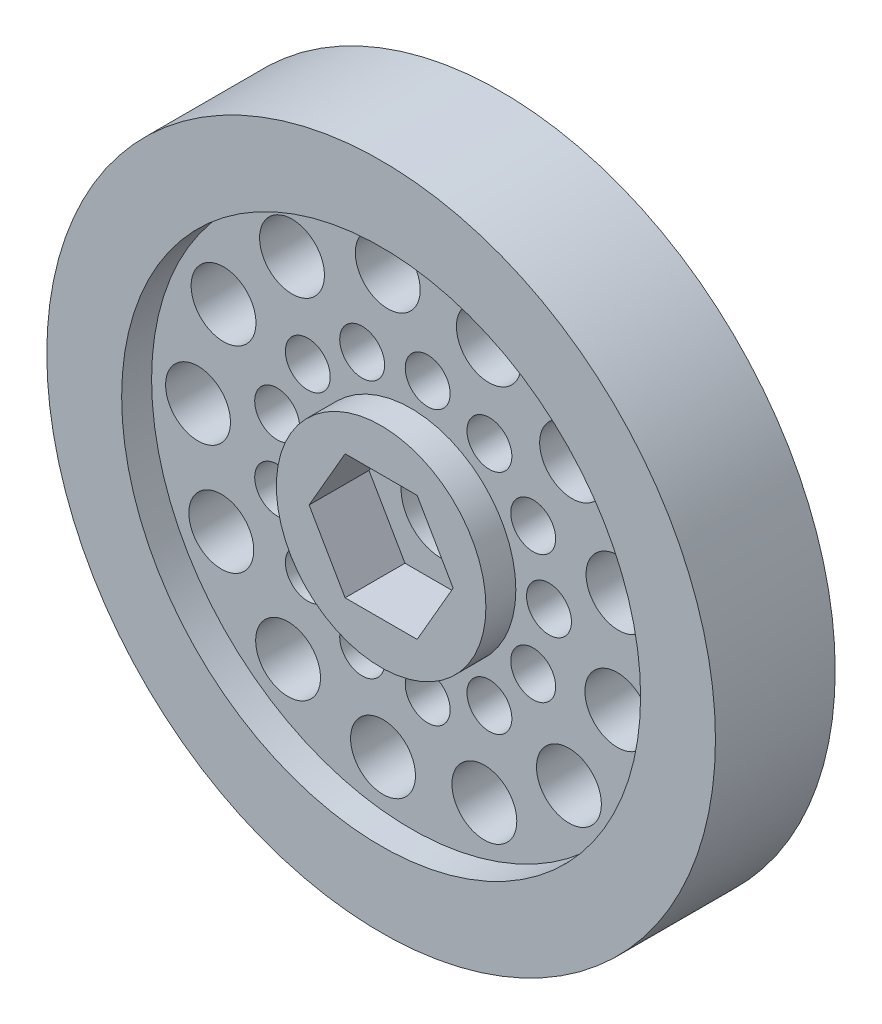
SolidWorks part; units mm, degrees
ref_plane "Front Plane" through (0, 0, 0) normal (0, 0, 1) x (1, 0, 0)
ref_plane "Top Plane" through (0, 0, 0) normal (0, 1, 0) x (1, 0, 0)
ref_plane "Right Plane" through (0, 0, 0) normal (1, 0, 0) x (0, 0, -1)
sketch "Sketch1" plane through (0, 0, 0) normal (0, 0, 1) x (1, 0, 0)
  circle A0 centre (0, 0) radius 4
  circle A1 centre (0, 0) radius 33.5
  dimension "D1" = 67
  dimension "D2" = 8
extrude "Boss-Extrude1" add sketch "Sketch1" along normal blind 12
sketch "Sketch2" plane through (0, 0, 12) normal (0, 0, 1) x (1, 0, 0)
  line L1 (7.2169, 0) -> (3.6084, 6.25)
  line L2 (3.6084, 6.25) -> (-3.6084, 6.25)
  line L3 (-3.6084, 6.25) -> (-7.2169, 0)
  line L4 (-7.2169, 0) -> (-3.6084, -6.25)
  line L5 (-3.6084, -6.25) -> (3.6084, -6.25)
  line L6 (3.6084, -6.25) -> (7.2169, 0)
  circle A0 centre (0, 0) radius 6.25 construction
  dimension "D1" = 12.5
extrude "Cut-Extrude1" cut sketch "Sketch2" against normal blind 6
sketch "Sketch3" plane through (0, 0, 12) normal (0, 0, 1) x (1, 0, 0)
  circle A0 centre (0, 0) radius 33.5 construction
  circle A1 centre (0, 0) radius 33.5 construction
  circle A2 centre (0, 0) radius 26
  circle A3 centre (0, 0) radius 10.5
  dimension "D1" = 7.5
  dimension "D2" = 23
extrude "Cut-Extrude2" cut sketch "Sketch3" against normal blind 3
sketch "Sketch4" plane through (0, 0, 0) normal (0, 0, -1) x (-1, 0, 0)
  circle A0 centre (0, 0) radius 10.5 construction
  circle A1 centre (0, 0) radius 26 construction
  circle A2 centre (0, 0) radius 10.5
  circle A3 centre (0, 0) radius 26
extrude "Cut-Extrude3" cut sketch "Sketch4" against normal blind 3
sketch "Sketch5" plane through (0, 0, 9) normal (0, 0, 1) x (1, 0, 0)
  line L0 (0, 0) -> (33.5, 0) construction
  line L1 (13.8207, 0) -> (20.7835, 4.8754) construction
  circle A0 centre (0, 0) radius 33.5 construction
  circle A1 centre (13.8207, 0) radius 2.25
  circle A2 centre (20.7835, 4.8754) radius 3.25
  dimension "D1" = 35
  dimension "D3" = 4.5
  dimension "D4" = 6.5
  dimension "D2" = 8.5
extrude "Cut-Extrude4" cut sketch "Sketch5" against normal blind 10
pattern_circular "CirPattern1" count 13 over 360 about axis through (0, 0, 6) along (0, 0, 1) of "Cut-Extrude4"
